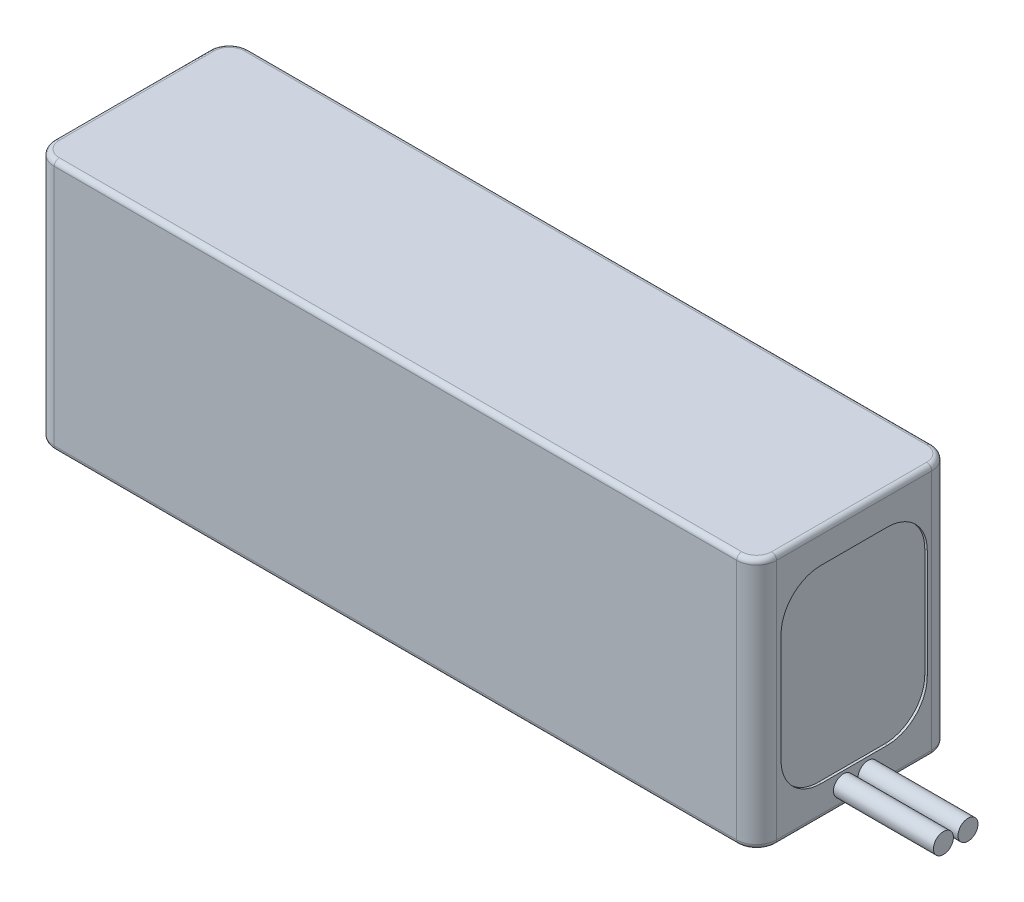
SolidWorks part; units mm, degrees
ref_plane "Front Plane" through (0, 0, 0) normal (0, 0, 1) x (1, 0, 0)
ref_plane "Top Plane" through (0, 0, 0) normal (0, 1, 0) x (1, 0, 0)
ref_plane "Right Plane" through (0, 0, 0) normal (1, 0, 0) x (0, 0, -1)
ref_plane "Plane1" through (0, 0, -15) normal (0, 0, -1) x (-1, 0, 0)
sketch "Sketch1" plane through (0, 0, -15) normal (0, 0, -1) x (-1, 0, 0)
  line L0 (-69, -22) -> (75.5, -22)
  line L1 (75.5, -22) -> (75.5, 28.4)
  line L2 (75.5, 28.4) -> (-69, 28.4)
  line L3 (-69, 28.4) -> (-69, -22)
  line L4 (-69, 3.2) -> (75.5, 3.2) construction
  line L5 (3.25, 28.4) -> (3.25, -22) construction
  dimension "D1" = 50.4
  dimension "D2" = 144.5
extrude "Boss-Extrude1" add sketch "Sketch1" against normal blind 39
sketch "Sketch2" plane through (69, 0, 0) normal (1, 0, 0) x (0, 0, -1)
  line L0 (-19.125, 14.1) -> (-19.125, -7.7)
  line L1 (-11.125, -15.7) -> (2.125, -15.7)
  line L2 (10.125, -7.7) -> (10.125, 14.1)
  line L3 (2.125, 22.1) -> (-11.125, 22.1)
  line L4 (-24, 28.4) -> (15, -22) construction
  line L5 (15, 28.4) -> (-24, -22) construction
  line L6 (-19.125, 22.1) -> (10.125, -15.7) construction
  line L7 (10.125, 22.1) -> (-19.125, -15.7) construction
  line L12 (-24, 28.4) -> (15, 28.4) construction
  line L13 (-24, 28.4) -> (-24, -22) construction
  line L14 (-24, -22) -> (15, -22) construction
  line L15 (15, 28.4) -> (15, -22) construction
  line L16 (-24, 28.4) -> (15, -22) construction
  line L17 (-24, -22) -> (15, 28.4) construction
  arc A0 (-19.125, -7.7) -> (-11.125, -15.7) centre (-11.125, -7.7) ccw
  arc A1 (2.125, -15.7) -> (10.125, -7.7) centre (2.125, -7.7) ccw
  arc A2 (10.125, 14.1) -> (2.125, 22.1) centre (2.125, 14.1) ccw
  arc A3 (-19.125, 14.1) -> (-11.125, 22.1) centre (-11.125, 14.1) cw
  point P16 (-4.5, 3.2)
  dimension "D3" = 8
  dimension "D1" = 29.25
  dimension "D2" = 39
extrude "Cut-Extrude1" cut sketch "Sketch2" against normal blind 0.5
sketch "Sketch3" plane through (-75.5, 0, 0) normal (-1, 0, 0) x (0, 0, 1)
  line L0 (11.125, 22.1) -> (-2.125, 22.1)
  line L1 (-10.125, 14.1) -> (-10.125, -7.7)
  line L2 (-2.125, -15.7) -> (11.125, -15.7)
  line L3 (19.125, -7.7) -> (19.125, 14.1)
  line L4 (-10.125, 22.1) -> (19.125, -15.7) construction
  line L5 (19.125, 22.1) -> (-10.125, -15.7) construction
  line L6 (-15, 28.4) -> (24, -22) construction
  line L7 (24, -22) -> (-15, -22) construction
  line L8 (-15, -22) -> (24, 28.4) construction
  arc A0 (-10.125, -7.7) -> (-2.125, -15.7) centre (-2.125, -7.7) ccw
  arc A1 (11.125, -15.7) -> (19.125, -7.7) centre (11.125, -7.7) ccw
  arc A2 (11.125, 22.1) -> (19.125, 14.1) centre (11.125, 14.1) cw
  arc A3 (-2.125, 22.1) -> (-10.125, 14.1) centre (-2.125, 14.1) ccw
  dimension "D3" = 8
  dimension "D1" = 29.25
  dimension "D2" = 39
extrude "Cut-Extrude2" cut sketch "Sketch3" against normal blind 0.5
fillet "Fillet1" radius 4 4 edges at (-75.5, 3.2, -15) (-75.5, 3.2, 24) (69, 3.2, -15) (69, 3.2, 24) tangent propagation no
fillet "Fillet2" radius 1 16 edges at (67.8284, 28.4, -13.8284) (69, 28.4, 4.5) (-3.25, 28.4, -15) (67.8284, 28.4, 22.8284) (-74.3284, 28.4, -13.8284) (-3.25, 28.4, 24) (-75.5, 28.4, 4.5) (-74.3284, 28.4, 22.8284) (-75.5, -22, 4.5) (-74.3284, -22, -13.8284) (-74.3284, -22, 22.8284) (-3.25, -22, -15) (-3.25, -22, 24) (67.8284, -22, -13.8284) (67.8284, -22, 22.8284) (69, -22, 4.5) tangent propagation no
sketch "Sketch4" plane through (0, 0, 24) normal (0, 0, 1) x (1, 0, 0)
  line L0 (-71.5, 3.2) -> (65, 3.2) construction
  line L1 (-71.5, 27.4) -> (-71.5, -21) construction
  line L2 (65, -21) -> (65, 27.4) construction
  line L3 (-3.25, 25.9735) -> (-3.25, -21) construction
  line L4 (-71.5, -21) -> (65, -21) construction
  circle A0 centre (-3.25, 3.2) radius 0.5026
sketch "Sketch5" plane through (69, 0, 0) normal (1, 0, 0) x (0, 0, -1)
  circle A0 centre (-1.7272, -18.4043) radius 2
  dimension "D1" = 4
extrude "Boss-Extrude2" add sketch "Sketch5" along normal blind 20 contours A0
sketch "Sketch6" plane through (69, 0, 0) normal (1, 0, 0) x (0, 0, -1)
  circle A0 centre (-6.641, -18.2529) radius 2
  dimension "D1" = 4
extrude "Boss-Extrude3" add sketch "Sketch6" along normal blind 20
equation "\"D1@Sketch3\"=\"D2@Sketch3\" * .75"
equation "\"D1@Sketch2\"=\"D2@Sketch2\"* .75"
